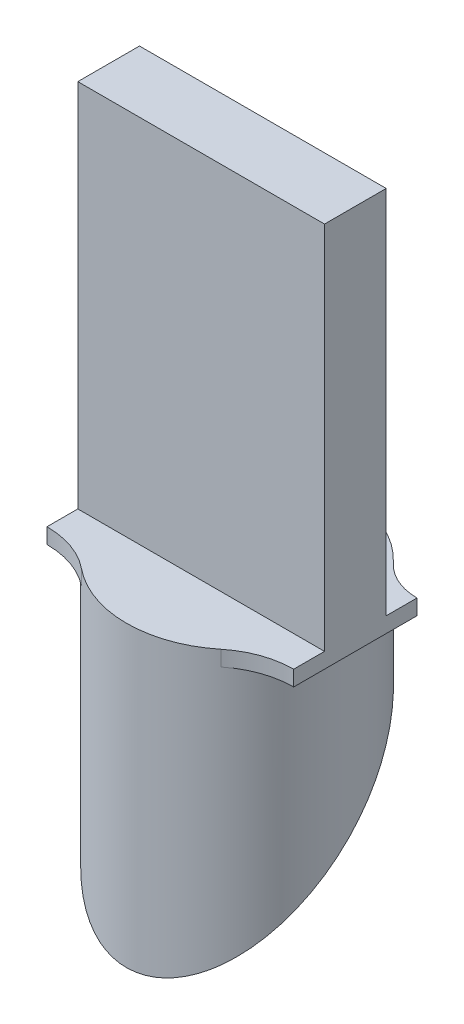
SolidWorks part; units mm, degrees
ref_plane "Front Plane" through (0, 0, 0) normal (0, 0, 1) x (1, 0, 0)
ref_plane "Top Plane" through (0, 0, 0) normal (0, 1, 0) x (1, 0, 0)
ref_plane "Right Plane" through (0, 0, 0) normal (1, 0, 0) x (0, 0, -1)
sketch "Sketch2" plane through (0, 0, 0) normal (1, 0, 0) x (0, 0, -1)
  line L0 (1.0414, 1052.7211) -> (1.0414, 994.4816) construction
  line L1 (1.0414, 1052.7211) -> (-21.7283, 1052.7211)
  line L2 (-21.7283, 1052.7211) -> (-21.7283, 994.4816)
  line L3 (-21.7283, 994.4816) -> (1.0414, 994.4816)
  line L4 (1.0414, 1052.7211) -> (1.0414, 994.4816)
revolve "Revolve1" add sketch "Sketch2" angle 360 about L0
sketch "Sketch3" plane through (0, 0, 0) normal (1, 0, 0) x (0, 0, -1)
  line L0 (-21.7283, 994.4816) -> (23.8111, 1040.0211)
  line L1 (23.8111, 1040.0211) -> (23.8111, 994.4816)
  line L2 (23.8111, 994.4816) -> (-21.7283, 994.4816)
extrude "Cut-Extrude1" cut sketch "Sketch3" against normal through all both and the other way through all
shell "Shell1" thickness 3.175 removed face at (0, 1040.0211, -23.8111)
sketch "Sketch4" plane through (0, 1052.7211, 0) normal (0, 1, 0) x (1, 0, 0)
  line L12 (25.4, 12.7) -> (-25.4, 12.7) construction
  line L13 (25.4, 12.7) -> (25.4, -12.7)
  line L14 (25.4, -12.7) -> (-25.4, -12.7) construction
  line L15 (-25.4, 12.7) -> (-25.4, -12.7)
  line L16 (25.4, 12.7) -> (-25.4, -12.7) construction
  line L17 (25.4, -12.7) -> (-25.4, 12.7) construction
  arc A0 (-25.4, 12.7) -> (-16.7213, 16.4965) centre (-25.4, 24.5179) ccw
  circle A1 centre (0, 1.0414) radius 22.7697
  arc A2 (-14.3712, -16.6202) -> (14.3712, -16.6202) centre (0, 1.0414) ccw
  arc A3 (16.7213, 16.4965) -> (25.4, 12.7) centre (25.4, 24.5179) ccw
  arc A4 (25.4, -12.7) -> (14.3712, -16.6202) centre (25.4, -30.1741) ccw
  arc A5 (-25.4, -12.7) -> (-14.3712, -16.6202) centre (-25.4, -30.1741) cw
  arc A6 (16.7213, 16.4965) -> (-16.7213, 16.4965) centre (0, 1.0414) ccw
  point P0 (0, 0)
  dimension "D1" = 25.4
  dimension "D2" = 50.8
  dimension "D3" = 0
extrude "Boss-Extrude1" add sketch "Sketch4" along normal blind 3.175
sketch "Sketch5" plane through (0, 1055.8961, 0) normal (0, 1, 0) x (1, 0, 0)
  line L0 (-25.4, 12.7) -> (-25.4, -12.7) construction
  line L1 (25.4, 6.35) -> (-25.4, 6.35)
  line L2 (25.4, 6.35) -> (25.4, -6.35)
  line L3 (25.4, -6.35) -> (-25.4, -6.35)
  line L4 (-25.4, 6.35) -> (-25.4, -6.35)
  line L5 (0, -6.35) -> (0, 6.35) construction
  line L6 (25.4, 0) -> (-25.4, 0) construction
  point P0 (0, 0)
  dimension "D1" = 12.7
extrude "Boss-Extrude2" add sketch "Sketch5" along normal blind 76.2
